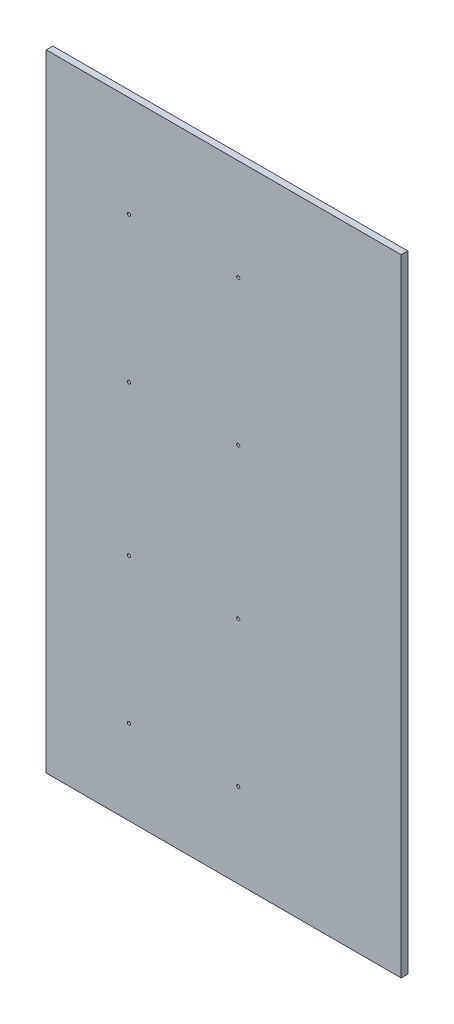
SolidWorks part; units mm, degrees
ref_plane "Front Plane" through (0, 0, 0) normal (0, 0, 1) x (1, 0, 0)
ref_plane "Top Plane" through (0, 0, 0) normal (0, 1, 0) x (1, 0, 0)
ref_plane "Right Plane" through (0, 0, 0) normal (1, 0, 0) x (0, 0, -1)
sketch "Sketch1" plane through (0, 0, 0) normal (0, 0, 1) x (1, 0, 0)
  line L1 (0, 0) -> (340, 0)
  line L2 (0, 0) -> (0, 600)
  line L3 (0, 600) -> (340, 600)
  line L4 (340, 0) -> (340, 600)
extrude "Sheet" add sketch "Sketch1" along normal blind 6.35
sketch "Sketch2" plane through (0, 0, 0) normal (0, 0, 1) x (1, 0, 0)
  circle A0 centre (183.95, 80.9) radius 1.5
  circle A1 centre (79.25, 80.9) radius 1.5
  circle A2 centre (183.95, 220.033) radius 1.5
  circle A3 centre (79.25, 220.033) radius 1.5
  circle A4 centre (183.95, 363.967) radius 1.5
  circle A5 centre (79.25, 363.967) radius 1.5
  circle A6 centre (183.95, 503.1) radius 1.5
  circle A7 centre (79.25, 503.1) radius 1.5
extrude "Holes" cut sketch "Sketch2" against normal through all and the other way through all
equation "\"t\" = 6.35mm"
equation "\"D1@Sheet\" = \"t\""
